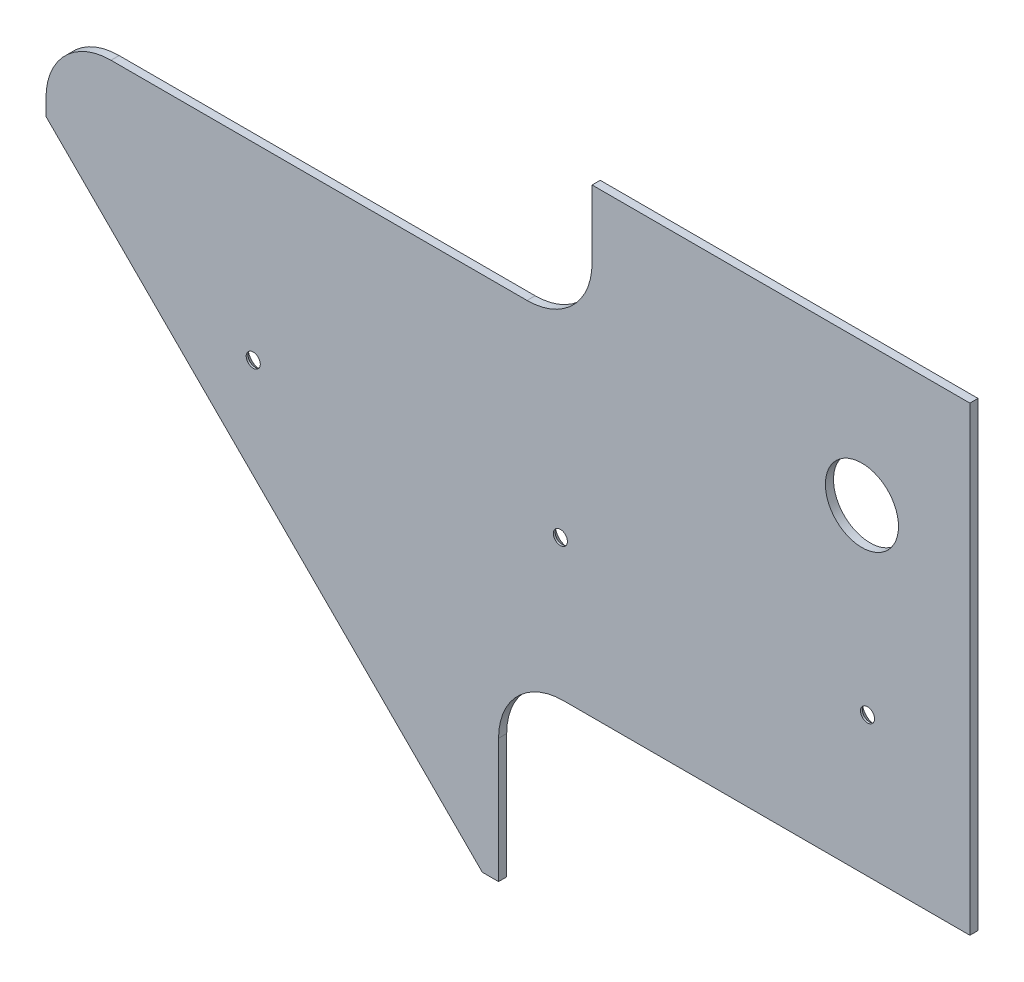
SolidWorks part; units mm, degrees
ref_plane "Front Plane" through (0, 0, 0) normal (0, 0, 1) x (1, 0, 0)
ref_plane "Top Plane" through (0, 0, 0) normal (0, 1, 0) x (1, 0, 0)
ref_plane "Right Plane" through (0, 0, 0) normal (1, 0, 0) x (0, 0, -1)
sketch "Sketch1" plane through (0, 0, 0) normal (0, 0, 1) x (1, 0, 0)
  line L0 (-138.2594, 48.9915) -> (32.2106, -121.4785)
  line L1 (32.2106, -121.4785) -> (222.7106, -121.4785)
  line L2 (-138.2594, 145.2215) -> (-138.2594, 48.9915)
  line L3 (-138.2594, 145.2215) -> (222.7106, 145.2215)
  line L4 (222.7106, -121.4785) -> (222.7106, 145.2215)
  circle A0 centre (180.538, 76.832) radius 14.2875
  circle A2 centre (180.538, 76.832) radius 64.9605 construction
  circle A3 centre (180.538, 76.832) radius 318.7974 construction
  point P0 (0, 0)
  point P2 (180.538, 76.832)
  dimension "D4" = 198.3105
  dimension "D1" = 45
  dimension "D2" = 266.7
  dimension "D5" = 245.11
extrude "Boss-Extrude1" add sketch "Sketch1" along normal blind 3.175
sketch "Sketch2" plane through (0, 0, 3.175) normal (0, 0, 1) x (1, 0, 0)
  line L0 (32.2106, -121.4785) -> (222.7106, -121.4785) construction
  line L1 (222.7634, -121.4785) -> (38.5606, -121.4785)
  line L2 (222.7634, -121.4785) -> (222.7634, -47.5645)
  line L3 (222.7634, -47.5645) -> (38.5606, -47.5645)
  line L4 (38.5606, -121.4785) -> (38.5606, -47.5645)
extrude "Cut-Extrude1" cut sketch "Sketch2" against normal through all contours L3 L4 L1 L2
fillet "Fillet1" radius 25.4 1 edges at (38.5606, -47.5645, 1.5875)
sketch "Sketch4" plane through (0, 0, 3.175) normal (0, 0, 1) x (1, 0, 0)
  line L1 (-138.2594, 145.2215) -> (-138.2594, 48.9915) construction
  line L3 (-138.2594, 145.2215) -> (75.1006, 145.2215)
  line L4 (-138.2594, 145.2215) -> (-138.2594, 80.7415)
  line L5 (-138.2594, 80.7415) -> (75.1006, 80.7415)
  line L6 (75.1006, 145.2215) -> (75.1006, 80.7415)
extrude "Cut-Extrude2" cut sketch "Sketch4" against normal through all contours L5 L6 L3 L4
fillet "Fillet2" radius 25.4 2 edges at (-138.2594, 80.7415, 1.5875) (75.1006, 80.7415, 1.5875)
sketch "Sketch7" plane through (0, 0, 3.175) normal (0, 0, 1) x (1, 0, 0)
  line L0 (222.7106, -47.5645) -> (222.7106, 145.2215) construction
  line L1 (75.1006, 145.2215) -> (222.7106, 145.2215)
  line L2 (75.1006, 145.2215) -> (75.1006, 132.5215)
  line L3 (75.1006, 132.5215) -> (222.7106, 132.5215)
  line L4 (222.7106, 145.2215) -> (222.7106, 132.5215)
  dimension "D1" = 12.7
extrude "Cut-Extrude4" cut sketch "Sketch7" against normal through all
hole_wizard "CSK for M5 Flat Head Machine Screw1" positions "Sketch9" profile "Sketch8" countersink size "M5" standard "ANSI Metric" end condition through all
sketch "Sketch9" plane through (0, 0, 0) normal (0, 0, -1) x (-1, 0, 0)
  point P0 (-182.7106, 7.0429)
  point P3 (-62.7106, 7.0429)
  point P6 (57.2894, 7.0429)
sketch "Sketch8" plane through (182.7106, 7.0429, 0) normal (1, 0, 0) x (0, 1, 0)
  line L0 (0, 0) -> (0, 3.175)
  line L1 (0, 3.175) -> (2.75, 3.175)
  line L2 (2.75, 3.175) -> (2.75, 2.45)
  line L3 (2.75, 2.45) -> (5.2, 0)
  line L5 (5.2, 0) -> (0, 0)
  line L6 (-2.75, 2.45) -> (-5.2, 0) construction
  line L11 (0, -6.35) -> (0, 107.95) construction
  dimension "Thru Hole Dia." = 5.5
  dimension "Thru Hole Depth" = 3.175
  dimension "Near C'Sink Dia." = 10.4
  dimension "Near C'Sink Angle" = 90
